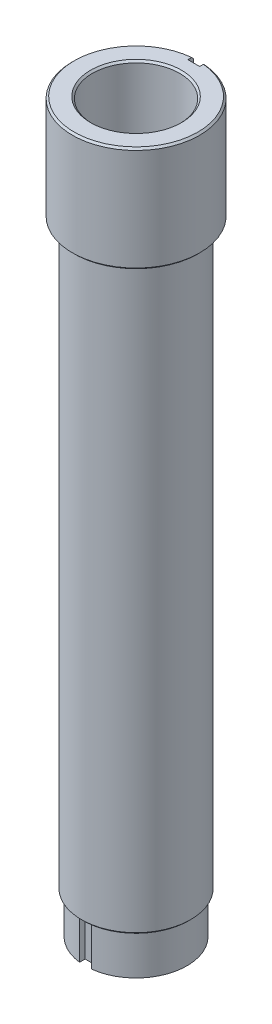
SolidWorks part; units mm, degrees
ref_plane "Front Plane" through (0, 0, 0) normal (0, 0, 1) x (1, 0, 0)
ref_plane "Top Plane" through (0, 0, 0) normal (0, 1, 0) x (1, 0, 0)
ref_plane "Right Plane" through (0, 0, 0) normal (1, 0, 0) x (0, 0, -1)
sketch "Sketch1" plane through (0, 0, 0) normal (0, 0, 1) x (1, 0, 0)
  line L0 (12, 200) -> (12, 0)
  line L1 (12, 0) -> (14, 0)
  line L2 (14, 0) -> (14, 11)
  line L6 (0, 0) -> (0, 16.1501) construction
  line L7 (14, 11) -> (15, 11)
  line L8 (15, 11) -> (15, 200)
  line L9 (12, 200) -> (15, 200)
  dimension "D1" = 12
  dimension "D2" = 14
  dimension "D3" = 15
  dimension "D4" = 11
  dimension "D5" = 200
revolve "Revolve1" add sketch "Sketch1" angle 360 about L6
ref_axis "Axis1" through (0, 250, 0) along (0, -1, 0)
sketch "Sketch2" plane through (0, 0, 0) normal (0, -1, 0) x (1, 0, 0)
  line L1 (-1.625, 15.625) -> (1.625, 15.625)
  line L2 (-1.625, 15.625) -> (-1.625, 12.375)
  line L3 (-1.625, 12.375) -> (1.625, 12.375)
  line L4 (1.625, 15.625) -> (1.625, 12.375)
  line L5 (-1.625, 15.625) -> (1.625, 12.375) construction
  line L6 (-1.625, 12.375) -> (1.625, 15.625) construction
  circle A0 centre (0, 0) radius 14 construction
  point P0 (0, 14)
  dimension "D1" = 3.25
extrude "Cut-Extrude1" cut sketch "Sketch2" against normal up to surface (11 mm away) up to face at (0, 11, -15)
chamfer "Chamfer1" distance 0.5 angle 45 1 edges at (0, 11, -15)
sketch "Sketch3" plane through (0, 200, 0) normal (0, 1, 0) x (1, 0, 0)
  circle A0 centre (0, 0) radius 17.5
  circle A1 centre (0, 0) radius 15 construction
  circle A2 centre (0, 0) radius 15
  dimension "D1" = 35
extrude "Boss-Extrude1" add sketch "Sketch3" against normal blind 29
sketch "Sketch4" plane through (0, 200, 0) normal (0, 1, 0) x (1, 0, 0)
  line L1 (-1.625, 19.125) -> (1.625, 19.125)
  line L2 (-1.625, 19.125) -> (-1.625, 15.875)
  line L3 (-1.625, 15.875) -> (1.625, 15.875)
  line L4 (1.625, 19.125) -> (1.625, 15.875)
  line L5 (-1.625, 19.125) -> (1.625, 15.875) construction
  line L6 (-1.625, 15.875) -> (1.625, 19.125) construction
  circle A0 centre (0, 0) radius 17.5 construction
  point P0 (0, 17.5)
  point P7 (0, 0)
  dimension "D1" = 3.25
extrude "Cut-Extrude2" cut sketch "Sketch4" against normal up to surface (29 mm away) up to face at (0, 171, 15)
chamfer "Chamfer2" distance 0.5 angle 45 4 edges at (0, 171, 15) (0, 200, 17.5) (0, 171, 17.5) (0, 200, -12)
